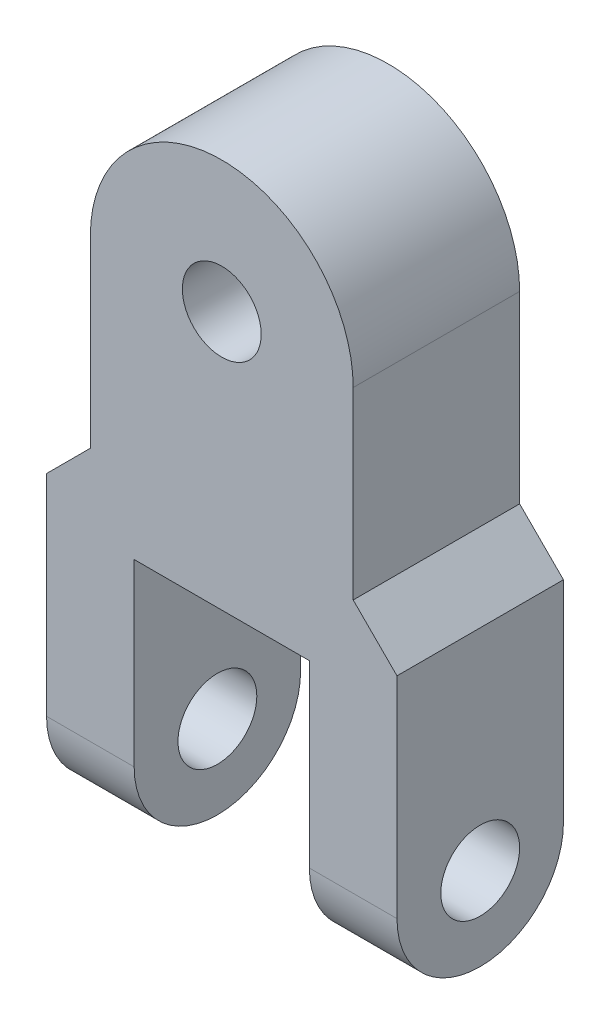
SolidWorks part; units mm, degrees
ref_plane "Front Plane" through (0, 0, 0) normal (0, 0, 1) x (1, 0, 0)
ref_plane "Top Plane" through (0, 0, 0) normal (0, 1, 0) x (1, 0, 0)
ref_plane "Right Plane" through (0, 0, 0) normal (1, 0, 0) x (0, 0, -1)
sketch "Sketch1" plane through (0, 0, 0) normal (0, 0, 1) x (1, 0, 0)
  line L1 (0, 0) -> (15, 0)
  line L2 (0, 0) -> (0, 10)
  line L4 (15, 0) -> (15, 10)
  arc A0 (0, 10) -> (15, 10) centre (7.5, 10) cw
  circle A1 centre (7.5, 10) radius 2.25
  dimension "D3" = 4.5
  dimension "D1" = 15
  dimension "D2" = 10
extrude "Boss-Extrude1" add sketch "Sketch1" along normal blind 9.5
ref_plane "Plane1" through (7.5, 0, 0) normal (1, 0, 0) x (0, 0, -1)
sketch "Sketch2" plane through (7.5, 0, 0) normal (1, 0, 0) x (0, 0, -1)
  line L0 (-9.5, 0) -> (-9.5, -15)
  line L1 (0, 0) -> (0, -15)
  line L2 (-9.5, 0) -> (0, 0)
  arc A0 (-9.5, -15) -> (0, -15) centre (-4.75, -15) ccw
  circle A1 centre (-4.75, -15) radius 2.25
  point P8 (0, 0)
  dimension "D2" = 4.5
  dimension "D1" = 15
extrude "Boss-Extrude2" add sketch "Sketch2" along normal blind 10 and the other way blind 10
sketch "Sketch4" plane through (5.5, 0, 9.5) normal (0, 0, -1) x (-1, 0, 0)
  line L0 (-2, 17.5) -> (-2, -19.75) construction
  line L1 (-12, -19.75) -> (8, -19.75) construction
  line L4 (-7, -19.75) -> (3, -19.75)
  line L5 (-7, -19.75) -> (-7, -4.75)
  line L6 (-7, -4.75) -> (3, -4.75)
  line L7 (3, -19.75) -> (3, -4.75)
  arc A0 (5.5, 10) -> (-9.5, 10) centre (-2, 10) ccw construction
  point P4 (-2, -4.75)
  point P5 (-2, 17.5)
  dimension "D1" = 10
  dimension "D2" = 15
extrude "Cut-Extrude1" cut sketch "Sketch4" along normal through all
chamfer "Chamfer1" distance 3 angle 45 2 edges at (-2.5, 0, 4.75) (17.5, 0, 4.75)
